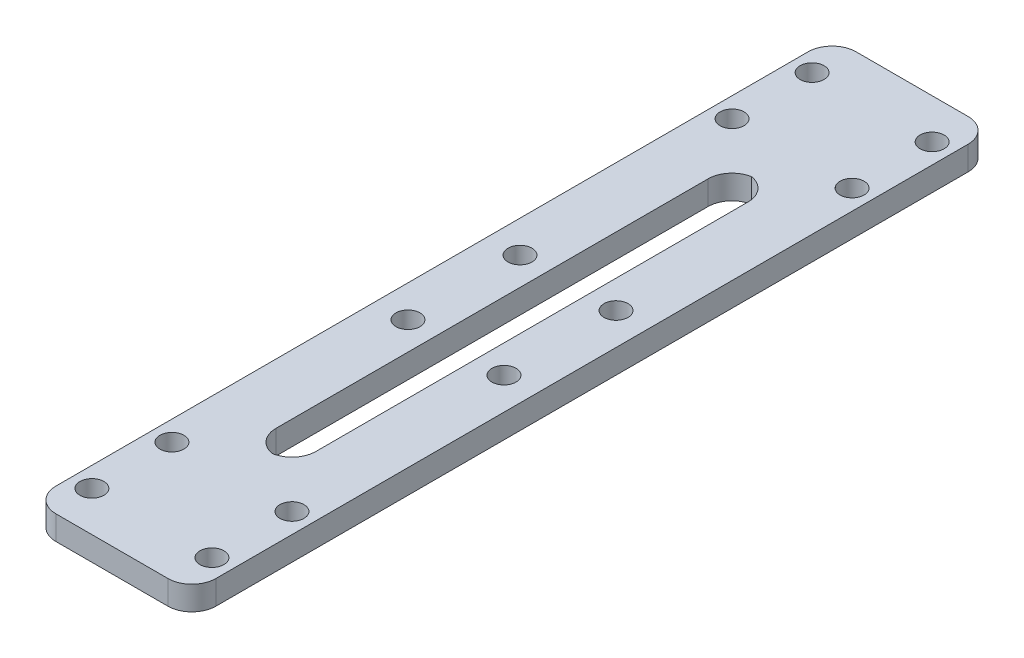
SolidWorks part; units mm, degrees
material "Thornel Mat VMA"
ref_plane "前视基准面" through (0, 0, 0) normal (0, 0, 1) x (1, 0, 0)
ref_plane "上视基准面" through (0, 0, 0) normal (0, 1, 0) x (1, 0, 0)
ref_plane "右视基准面" through (0, 0, 0) normal (1, 0, 0) x (0, 0, -1)
sketch "草图1" plane through (0, 0, 0) normal (0, 1, 0) x (1, 0, 0)
  line L1 (-10, -50) -> (10, -50)
  line L2 (-10, -50) -> (-10, 50)
  line L3 (-10, 50) -> (10, 50)
  line L4 (10, -50) -> (10, 50)
  line L5 (-10, -50) -> (10, 50) construction
  line L6 (-10, 50) -> (10, -50) construction
  point P0 (0, 0)
  dimension "D1" = 20
  dimension "D2" = 100
extrude "凸台-拉伸1" add sketch "草图1" along normal blind 3
sketch "草图2" plane through (0, 3, 0) normal (0, 1, 0) x (1, 0, 0)
  line L0 (-10, 0) -> (10, 0) construction
  line L1 (-10, 50) -> (-10, -50) construction
  line L2 (10, -50) -> (10, 50) construction
  line L3 (0, 50) -> (0, -50) construction
  line L4 (10, 50) -> (-10, 50) construction
  line L5 (-10, -50) -> (10, -50) construction
  line L6 (-7.5, -45) -> (7.5, -35) construction
  line L7 (-7.5, 35) -> (7.5, 35) construction
  line L8 (-7.5, 35) -> (-7.5, 45) construction
  line L9 (-7.5, 45) -> (7.5, 45) construction
  line L10 (7.5, 35) -> (7.5, 45) construction
  line L11 (-7.5, 35) -> (7.5, 45) construction
  line L12 (-7.5, 45) -> (7.5, 35) construction
  line L13 (-7.5, -35) -> (7.5, -45) construction
  line L14 (7.5, -35) -> (7.5, -45) construction
  line L15 (-7.5, -45) -> (7.5, -45) construction
  line L16 (-7.5, -35) -> (-7.5, -45) construction
  line L17 (-7.5, -35) -> (7.5, -35) construction
  circle A0 centre (-7.5, 45) radius 1.5
  circle A1 centre (-7.5, 35) radius 1.5
  circle A2 centre (7.5, 45) radius 1.5
  circle A3 centre (7.5, 35) radius 1.5
  circle A4 centre (7.5, -35) radius 1.5
  circle A5 centre (7.5, -45) radius 1.5
  circle A6 centre (-7.5, -35) radius 1.5
  circle A7 centre (-7.5, -45) radius 1.5
  point P12 (0, 40)
  point P29 (0, -40)
  dimension "D3" = 3
  dimension "D4" = 3
  dimension "D1" = 15
  dimension "D2" = 10
  dimension "D5" = 40
extrude "切除-拉伸1" cut sketch "草图2" against normal through all
sketch "草图3" plane through (0, 3, 0) normal (0, 1, 0) x (1, 0, 0)
  line L1 (-2.5, -30) -> (2.5, -30)
  line L2 (-2.5, -30) -> (-2.5, 30)
  line L3 (-2.5, 30) -> (2.5, 30)
  line L4 (2.5, -30) -> (2.5, 30)
  line L5 (-2.5, -30) -> (2.5, 30) construction
  line L6 (-2.5, 30) -> (2.5, -30) construction
  point P0 (0, 0)
  dimension "D1" = 60
  dimension "D2" = 5
extrude "切除-拉伸2" cut sketch "草图3" against normal through all and the other way through all
fillet "圆角1" radius 3 4 edges at (-2.5, 1.5, -30) (2.5, 1.5, -30) (-2.5, 1.5, 30) (2.5, 1.5, 30)
fillet "圆角2" radius 3 4 edges at (10, 1.5, -50) (-10, 1.5, -50) (-10, 1.5, 50) (10, 1.5, 50)
sketch "草图4" plane through (0, 3, 0) normal (0, 1, 0) x (1, 0, 0)
  line L0 (0, 7) -> (0, -7) construction
  line L1 (-6, -7) -> (6, -7) construction
  line L2 (-6, -7) -> (-6, 7) construction
  line L3 (-6, 7) -> (6, 7) construction
  line L4 (6, -7) -> (6, 7) construction
  line L5 (-6, -7) -> (6, 7) construction
  line L6 (-6, 7) -> (6, -7) construction
  line L7 (-6, 0) -> (6, 0) construction
  circle A0 centre (-6, 7) radius 1.5
  circle A1 centre (6, 7) radius 1.5
  circle A2 centre (6, -7) radius 1.5
  circle A3 centre (-6, -7) radius 1.5
  point P0 (0, 0)
  dimension "D1" = 3
  dimension "D2" = 14
  dimension "D3" = 12
extrude "切除-拉伸3" cut sketch "草图4" against normal through all
